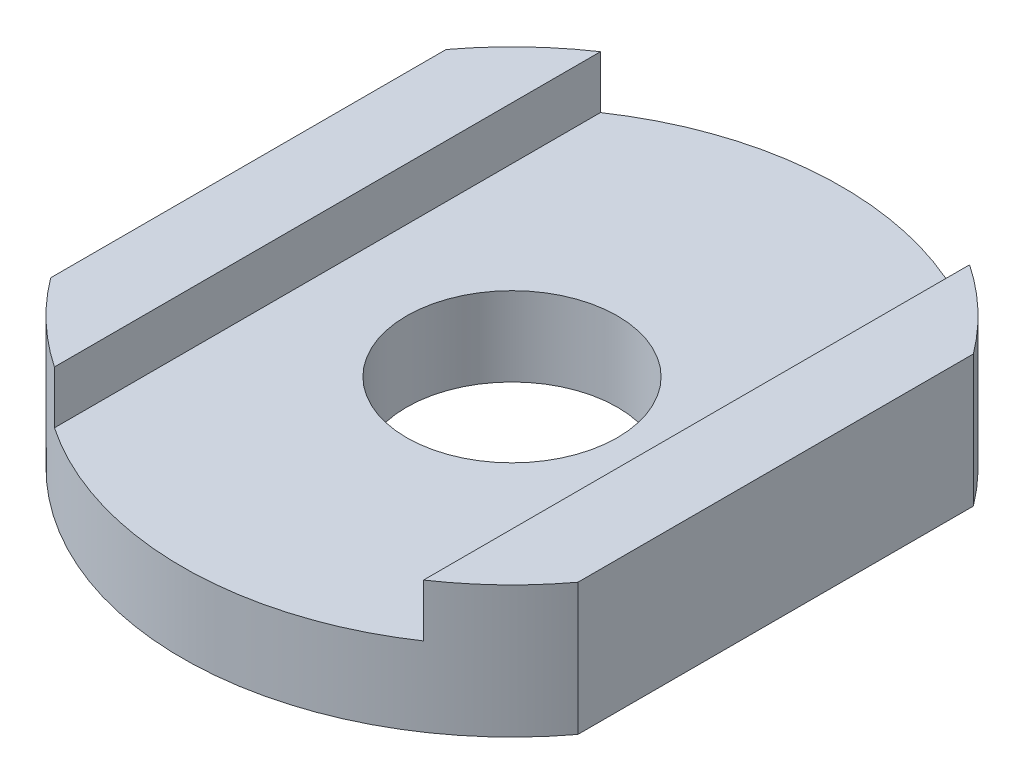
SolidWorks part; units mm, degrees
ref_plane "Front Plane" through (0, 0, 0) normal (0, 0, 1) x (1, 0, 0)
ref_plane "Top Plane" through (0, 0, 0) normal (0, 1, 0) x (1, 0, 0)
ref_plane "Right Plane" through (0, 0, 0) normal (1, 0, 0) x (0, 0, -1)
sketch "Sketch1" plane through (0, 0, 0) normal (0, 1, 0) x (1, 0, 0)
  line L0 (10, 7.5) -> (10, -7.5)
  line L1 (7, 10.3562) -> (7, -10.3562)
  line L2 (0, -13.75) -> (0, 13.75) construction
  line L3 (-7, 10.3562) -> (-7, -10.3562)
  line L4 (-10, 7.5) -> (-10, -7.5)
  arc A0 (-10, -7.5) -> (10, -7.5) centre (0, 0) ccw
  arc A1 (10, 7.5) -> (-10, 7.5) centre (0, 0) ccw
  circle A2 centre (0, 0) radius 4
  dimension "D1" = 25
  dimension "D4" = 8
  dimension "D2" = 10
  dimension "D3" = 3
extrude "Boss-Extrude1" add sketch "Sketch1" along normal blind 3 contours L1 A1 L3 A0 A2 | L3 A1 L4 A0 | L0 A1 L1 A0 region at (8.4223, 0, 0) region at (6.7135, 0, 0) region at (-8.4223, 0, 0)
extrude "Boss-Extrude2" add sketch "Sketch1<3>" along normal blind 5 contours L3 A1 L4 A0 | L0 A1 L1 A0 region at (8.4223, 0, 0) region at (-8.4223, 0, 0)
sketch "Sketch1<3>" plane through (0, 0, 0) normal (0, 1, 0) x (1, 0, 0) same geometry as "Sketch1"
